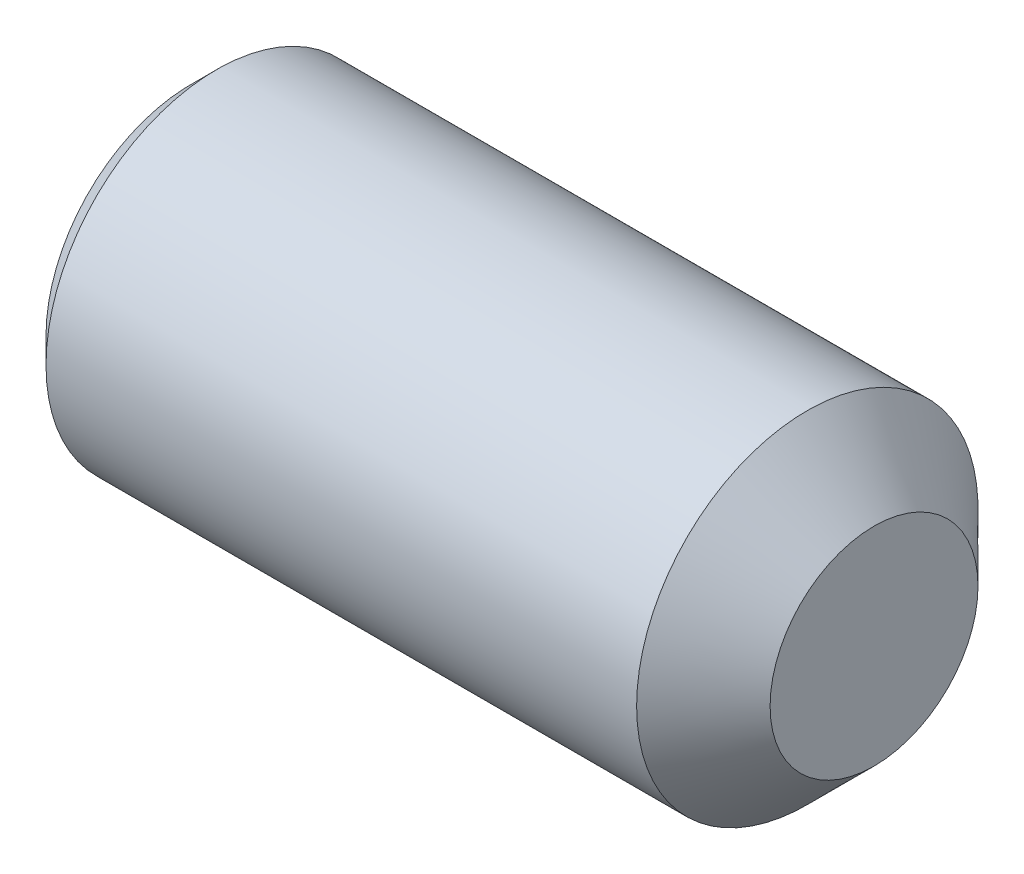
SolidWorks part; units mm, degrees
revolve "BaseBody" add sketch "BodySke" angle 360 about L5 other way angle 60
sketch "BodySke" plane through (0, 0, 0) normal (0, 0, 1) x (1, 0, 0)
  line L0 (0, 0) -> (0, 10.8102)
  line L1 (0, 10.8102) -> (1.8898, 12.7)
  line L2 (1.8898, 12.7) -> (45.8343, 12.7)
  line L3 (45.8343, 12.7) -> (50.8, 7.7343)
  line L4 (50.8, 0) -> (0, 0)
  line L5 (-12.7, 0) -> (88.9, 0) construction
  line L6 (50.8, 7.7343) -> (50.8, 0)
  line L7 (50.8, 7.7343) -> (50.8, 17.2593) construction
  line L8 (0, -10.8102) -> (1.8898, -12.7) construction
  line L9 (2.1082, 15.875) -> (2.1082, -3.175) construction
  line L10 (45.8343, -12.7) -> (50.8, -7.7343) construction
  dimension "Length" = 50.8
  dimension "Diameter" = 25.4
cosmetic thread "ThreadCosmetic" [suppressed] parameters "Thread_minor"=21.6205
ref_plane "Plane1" through (0, 0, 0) normal (0, 0, 1) x (1, 0, 0)
ref_plane "Plane2" through (0, 0, 0) normal (0, 1, 0) x (1, 0, 0)
ref_plane "Plane3" through (0, 0, 0) normal (1, 0, 0) x (0, 0, -1)
sketch "Sketch2" plane through (0, 0, 0) normal (-1, 0, 0) x (0, 0, 1)
  line L0 (4.1208, 7.1374) -> (-4.1208, 7.1374)
  line L1 (-4.1208, 7.1374) -> (-8.2416, 0)
  line L2 (4.1208, 7.1374) -> (8.2416, 0)
  line L3 (4.1208, -7.1374) -> (8.2416, 0)
  line L4 (4.1208, -7.1374) -> (-4.1208, -7.1374)
  line L5 (-4.1208, -7.1374) -> (-8.2416, 0)
  dimension "D2" = 7.1374
  dimension "D3" = 7.1374
extrude "Hex" cut sketch "Sketch2" against normal blind 14.2748
sketch "Sketch4" plane through (0, 4.7709, -0.5249) normal (-1, 0, 0) x (0, 0, 1)
  line L0 (0.5249, -4.7709) -> (10.6976, -4.7709)
  line L1 (0.5249, -4.7709) -> (6.6732, -1.2211) construction
  line L2 (0.5249, -4.7709) -> (5.6112, 4.0389)
  line L3 (8.9666, -2.6687) -> (10.2861, -1.9069)
  line L4 (6.5663, 1.4888) -> (7.8858, 2.2506)
  arc A0 (8.9666, -2.6687) -> (6.5663, 1.4888) centre (0.5249, -4.7709) ccw
  arc A1 (10.6976, -4.7709) -> (10.2861, -1.9069) centre (0.5249, -4.7709) ccw
  arc A2 (5.6112, 4.0389) -> (7.8858, 2.2506) centre (0.5249, -4.7709) cw
  circle A3 centre (0.5249, -4.7709) radius 8.6995 construction
  circle A4 centre (0.5249, -4.7709) radius 10.1727 construction
  dimension "Spline_n_dim" = 17.399
  dimension "Spline_m_dim" = 20.3454
  dimension "D1" = 30
  dimension "Spline_p_dim" = 4.8006
  dimension "D3" = 2.4003
extrude "Spline" [suppressed] cut sketch "Sketch4" against normal blind 12.7
pattern_circular "CirPattern1" [suppressed] count 6 every 60 about axis through (-12.7, 0, 0) along (1, 0, 0)
sketch "ThdSchSke" plane through (0, 0, 0) normal (0, 0, 1) x (1, 0, 0)
  line L0 (1.8898, -10.8102) -> (0.5665, -12.7)
  line L1 (1.8898, -10.8102) -> (3.213, -12.7)
  line L2 (3.213, -12.7) -> (3.213, -15.875)
  line L3 (-3.175, 0) -> (5.1513, 0) construction
  line L4 (1.8898, 12.7) -> (1.8898, -12.7) construction
  line L5 (3.213, -15.875) -> (0.5665, -15.875)
  line L6 (0.5665, -15.875) -> (0.5665, -12.7)
  dimension "Thread_minor" = 21.6205
  dimension "Diameter" = 25.4
revolve "ThreadSchematic" [suppressed] cut sketch "ThdSchSke" angle 360 about L3
pattern_linear "ThdSchPat" [suppressed]
equation "\"D2@Sketch2\" = \"Hex_size@Sketch2\" / 2"
equation "\"D3@Sketch2\" = \"Hex_size@Sketch2\" / 2"
equation "\"Thread_minor@ThreadCosmetic\" = \"Minor_dia@BodySke\""
equation "\"D1@Sketch4\" = \"Spline_a_dim@Sketch4\" / 2"
equation "\"D3@Sketch4\" = \"Spline_p_dim@Sketch4\" / 2"
equation "\"D2@CirPattern1\" = \"Spline_a_dim@Sketch4\""
equation "\"Num_teeth@CirPattern1\" = 360 / \"D2@CirPattern1\""
equation "\"Thread_minor@ThdSchSke\" = \"Thread_minor@ThreadCosmetic\""
equation "\"Diameter@ThdSchSke\" = \"Diameter@BodySke\""
equation "\"Overcut@ThdSchSke\" = \"Diameter@BodySke\" * 1.25"
equation "\"Num_threads@ThdSchPat\" = int( (\"Length@BodySke\" - ( ( ( \"Diameter@BodySke\" - \"Minor_dia@BodySke\" ) * 0.5 ) / tan( \"Drive_ch_ang@BodySke\" * 0.017453292 ) ) - ( ( ( \"Diameter@BodySke\" - \"Cup_dia@BodySke\" ) * 0.5 ) * tan( \"Cup_nose_ang@BodySke\" * 0.017453292 ) ) ) / \"Advance@BodySke\" + 0.999 )  + 1"
equation "\"Advance@ThdSchPat\" = (\"Length@BodySke\" - ( ( ( \"Diameter@BodySke\" - \"Minor_dia@BodySke\" ) * 0.5 ) / tan( \"Drive_ch_ang@BodySke\" * 0.017453292 ) ) - ( ( ( \"Diameter@BodySke\" - \"Cup_dia@BodySke\" ) * 0.5 ) * tan( \"Cup_nose_ang@BodySke\" * 0.017453292 ) ) ) /  (\"Num_threads@ThdSchPat\" - 1) 'relax it"
equation "' \"Num_threads@ThdSchPat\" = \"Num_threads@ThdSchPat\" - sgn( \"Num_threads@ThdSchPat\" - 1) '---chamfered tips only---"
